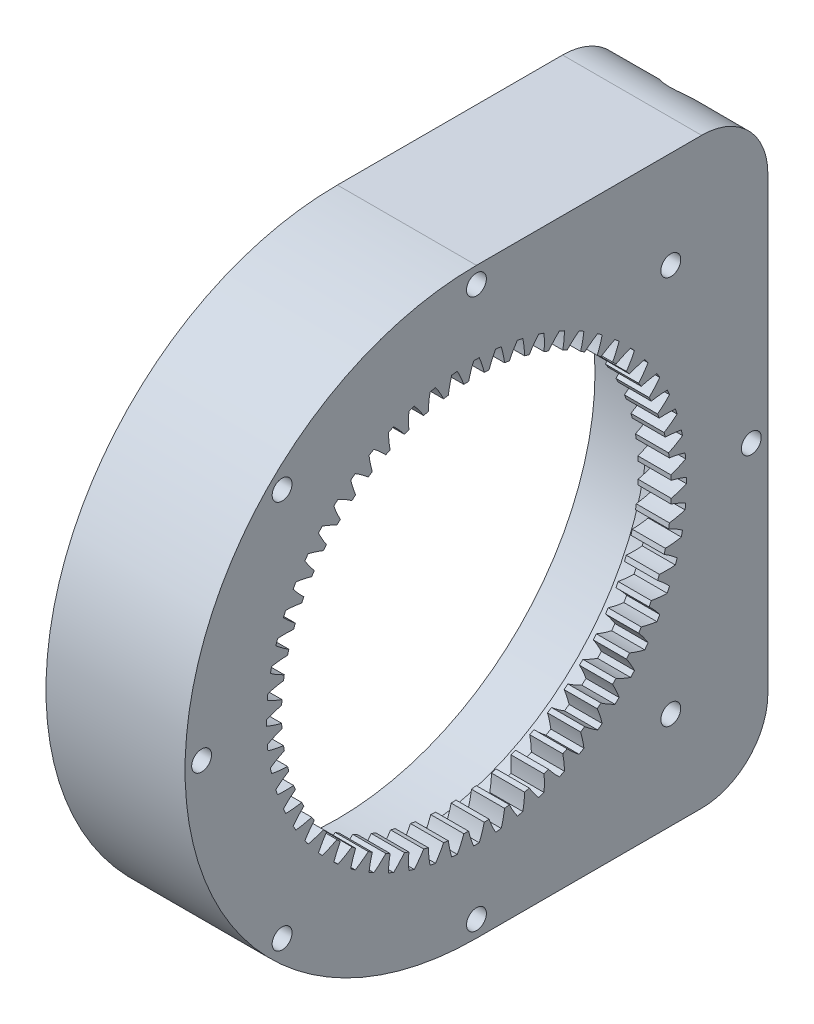
SolidWorks part; units mm, degrees
ref_plane "Plane1" through (0, 0, 0) normal (0, 0, 1) x (1, 0, 0)
ref_plane "Plane2" through (0, 0, 0) normal (0, 1, 0) x (1, 0, 0)
ref_plane "Plane3" through (0, 0, 0) normal (1, 0, 0) x (0, 0, -1)
other "Configuration Table"
sketch "HoldingSke" plane through (0, 0, 0) normal (0, 1, 0) x (1, 0, 0)
  line L0 (0, 0) -> (0.4926, -0.8532)
  line L1 (-15, 0) -> (100, 0) construction
  line L2 (0, 0) -> (-2.1039, 2.3779)
  line L3 (0, 0) -> (-11.863, 4.5341)
  line L4 (0, 0) -> (4.318, 7.479)
  line L5 (0, 0) -> (-23.7986, -8.8762)
  line L6 (0, 0) -> (-10.5278, -7.1032)
  line L7 (-2.1039, 2.3779) -> (3.3635, 27.1825)
  line L8 (-76.2, 3.3929) -> (-54.61, 3.3929)
  line L9 (-67.7845, 28.3722) -> (-49.3413, 33.142)
  line L10 (-76.2, 71.12) -> (104.1128, 71.12)
  line L11 (0, 0) -> (-5, 0)
  line L12 (-76.2, 101.6) -> (-76.162, 101.6)
  line L13 (24.9733, 27.94) -> (52.9518, 28.4284)
  line L14 (24.9733, 27.94) -> (24.9743, 27.94)
  line L15 (24.9733, 27.94) -> (100.4006, 29.5858)
  circle A0 centre (0, 0) radius 44
  circle A1 centre (0, 0) radius 12.7
  circle A2 centre (0, 0) radius 12.7
  dimension "Num_teeth" = 60
  dimension "Pitch_radius" = 180.3128
  dimension "Width" = 5
  dimension "Diameter" = 88
sketch "BasProSke" plane through (0, 0, 0) normal (0, 1, 0) x (1, 0, 0)
  line L0 (-10, 0) -> (60, 0) construction
  line L1 (0, 29.435) -> (0, 44)
  line L2 (0, 29.435) -> (5, 29.435)
  line L3 (5, 29.435) -> (5, 44)
  line L4 (5, 44) -> (0, 44)
  dimension "Thickness" = 5
  dimension "Diameter" = 88
revolve "Base-Revolve" add sketch "BasProSke" angle 360 about L0
sketch "TooCutSke" plane through (0, 0, 0) normal (1, 0, 0) x (0, 0, -1)
  line L3 (0.8921, 30.4369) -> (0.8921, 53.6633) construction
  line L4 (0, 0) -> (0, 59.563) construction
  line L5 (0, 0) -> (-3.576, 68.2339) construction
  line L6 (-13.6269, 25.8543) -> (36.4024, 28.4763) construction
  circle A0 centre (0, 0) radius 30.45 construction
  circle A1 centre (0, 0) radius 31.7197 construction
  circle A2 centre (0, 0) radius 26.5321 construction
  circle A3 centre (0, 0) radius 29.4096 construction
  arc A4 (1.1829, 29.3858) -> (0.4241, 31.7169) centre (-13.6269, 25.8543) ccw
  arc A5 (1.1829, 29.3858) -> (-1.1829, 29.3858) centre (0, 0) ccw
  arc A6 (0.4241, 31.7169) -> (-0.4241, 31.7169) centre (0, 0) ccw
  arc A7 (-0.4241, 31.7169) -> (-1.1829, 29.3858) centre (13.6269, 25.8543) ccw
extrude "ToothCut" cut sketch "TooCutSke" along normal through all
fillet "Breaks" [suppressed] radius 0.1015
fillet "RootFillets" [suppressed] radius 0.2547
pattern_circular "TeethCuts" count 60 every 6 about axis through (-10, 0, 0) along (1, 0, 0) of "RootFillets", "Breaks", "ToothCut"
sketch "Sketch4" plane through (0, 0, 0) normal (-1, 0, 0) x (0, 0, 1)
  circle A0 centre (0, 0) radius 44
  circle A1 centre (0, 0) radius 38.9
  circle A2 centre (0, 0) radius 44 construction
  dimension "D1" = 77.8
extrude "Boss-Extrude3" add sketch "Sketch4" along normal blind 16
sketch "Sketch7" plane through (5, 0, 0) normal (1, 0, 0) x (0, 0, -1)
  line L0 (0, 44) -> (44, 44)
  line L1 (44, 44) -> (44, 0)
  circle A0 centre (0, 0) radius 44 construction
  arc A1 (44, 0) -> (0, 44) centre (0, 0) ccw
extrude "Boss-Extrude5" add sketch "Sketch7" against normal up to surface (21 mm away) up to face at (-16, 0, 44)
sketch "Sketch10" plane through (5, 0, 0) normal (1, 0, 0) x (0, 0, -1)
  line L0 (0, -44) -> (44, -44)
  line L1 (44, -44) -> (44, 0)
  line L2 (44, 0) -> (44, 44) construction
  circle A0 centre (0, 0) radius 44 construction
  arc A1 (0, -44) -> (44, 0) centre (0, 0) ccw
  dimension "D1" = 180
extrude "Boss-Extrude6" add sketch "Sketch10" against normal up to surface (21 mm away) up to face at (-16, 11.6291, -11.6291)
fillet "Fillet1" radius 10 2 edges at (-5.5, 44, -44) (-5.5, -44, -44)
sketch "Sketch14" plane through (0, 0, 0) normal (-1, 0, 0) x (0, 0, 1)
  circle A0 centre (0, 0) radius 36.9
  circle A1 centre (0, 0) radius 38.9 construction
  circle A2 centre (0, 0) radius 38.9
  dimension "D1" = 2
extrude "Boss-Extrude7" add sketch "Sketch14" along normal blind 6
sketch "Sketch15" plane through (0, 0, -44) normal (0, 0, -1) x (-1, 0, 0)
  line L0 (-5, -34) -> (16, -34) construction
  line L1 (16, -44) -> (-5, -44) construction
  line L2 (-5, 44) -> (16, 44) construction
  circle A0 centre (5.5, -38) radius 4.25
  circle A1 centre (5.5, 38) radius 4.25
  point P4 (5.5, -34)
  dimension "D1" = 8.5
  dimension "D2" = 6
  dimension "D3" = 6
extrude "Cut-Extrude1" cut sketch "Sketch15" against normal blind 20
chamfer "Chamfer1" distance 10 angle 1 2 edges at (-9.75, 38, -24) (-9.75, -38, -24) first distance on face at (-5.612, 37.997, -41.83) first distance on face at (-5.388, -37.997, -41.83)
sketch "Sketch16" plane through (-16, 0, 0) normal (-1, 0, 0) x (0, 0, 1)
  circle A0 centre (41.5, 0) radius 1.5
  dimension "D2" = 3
  dimension "D1" = 41.5
extrude "Cut-Extrude3" cut sketch "Sketch16" against normal blind 30
pattern_circular "CirPattern1" count 8 over 360 about axis through (-10, 0, 0) along (-1, 0, 0) of "Cut-Extrude3"
equation "' \"Module@HoldingSke\" = 6.35"
equation "' \"Num_teeth@HoldingSke\" = 24"
equation "' \"Ap@HoldingSke\" =  14.5"
equation "' \"Ap@HoldingSke\" = 14.5"
equation "' \"Width@HoldingSke\" = 12"
equation "' \"Diameter@HoldingSke\" = 8 * 25.4"
equation "' \"Show_teeth@HoldingSke\" = 100"
equation "' \"Backlash@HoldingSke\" = 0.009 * 25.4"
equation "' \"Addendum_fac@HoldingSke\" = 1.0"
equation "' \"Dedendum_fac@HoldingSke\" = 1.25"
equation "' \"Dedendum_add@HoldingSke\" = 0.00005 * 25.4"
equation "' \"Clearance_fac@HoldingSke\" = 0.25"
equation "\"Pitch@HoldingSke\" = 1 / \"Module@HoldingSke\" "
equation "\"Overcut_dia@TooCutSke\" = (\"Num_teeth@HoldingSke\" - 2 * \"Addendum_fac@HoldingSke\") / \"Pitch@HoldingSke\" - 0.002 * 25.4"
equation "\"Pitch_dia@TooCutSke\" = \"Num_teeth@HoldingSke\" / \"Pitch@HoldingSke\""
equation "\"Base_dia@TooCutSke\" = \"Num_teeth@HoldingSke\" / \"Pitch@HoldingSke\" * cos((\"Ap@HoldingSke\"  * 3.14159265 / 180)) * 0.90"
equation "\"Root_dia@TooCutSke\" = \"Num_teeth@HoldingSke\"  / \"Pitch@HoldingSke\" + 2 *  \"Dedendum_fac@HoldingSke\"/ \"Pitch@HoldingSke\" + \"Dedendum_add@HoldingSke\" * 2"
equation "\"Half_ang@TooCutSke\" = 180 / \"Num_teeth@HoldingSke\""
equation "\"Half_CT@TooCutSke\" = \"Num_teeth@HoldingSke\" / \"Pitch@HoldingSke\" * sin((3.14159265 / 2 / \"Num_teeth@HoldingSke\")) / 2 + 10 * \"Backlash@HoldingSke\" / 4"
equation "\"Flank_rad@TooCutSke\" = \"Num_teeth@HoldingSke\" / \"Pitch@HoldingSke\" / 4"
equation "\"Radius@RootFillets\"= \"Clearance_fac@HoldingSke\" / \"Pitch@HoldingSke\" + \"Dedendum_add@HoldingSke\""
equation "\"Break_rad@Breaks\" = 0.02 / \"Pitch@HoldingSke\" * 5"
equation "\"Num_teeth@TeethCuts\" = int( \"Show_teeth@HoldingSke\" ) + 1"
equation "\"Num_teeth@TeethCuts\" = ((sgn( \"Num_teeth@TeethCuts\" - \"Num_teeth@HoldingSke\" )-1)*( \"Num_teeth@TeethCuts\" - \"Num_teeth@HoldingSke\" ))/-2+ \"Num_teeth@HoldingSke\""
equation "\"Num_teeth@TeethCuts\" = ((sgn( \"Num_teeth@TeethCuts\" - 2.0)+1)*( \"Num_teeth@TeethCuts\" - 2.0))/2 +2.0"
equation "\"Angle@TeethCuts\" = 360.0 / \"Num_teeth@HoldingSke\""
equation "\"Diameter@BasProSke\" = \"Num_teeth@HoldingSke\"  / \"Pitch@HoldingSke\" + 2 *  \"Dedendum_fac@HoldingSke\"/ \"Pitch@HoldingSke\" + \"Dedendum_add@HoldingSke\" * 2 + 0.002 * 25.4"
equation "\"Diameter@BasProSke\" = ((sgn( \"Diameter@BasProSke\"  - \"Diameter@HoldingSke\" )+1)*( \"Diameter@BasProSke\"  - \"Diameter@HoldingSke\" ))/2 + \"Diameter@HoldingSke\""
equation "\"Inside_diameter@BasProSke\" =  (\"Num_teeth@HoldingSke\" - 2 * \"Addendum_fac@HoldingSke\") / \"Pitch@HoldingSke\" "
equation "\"Thickness@BasProSke\"  = \"Width@HoldingSke\""
